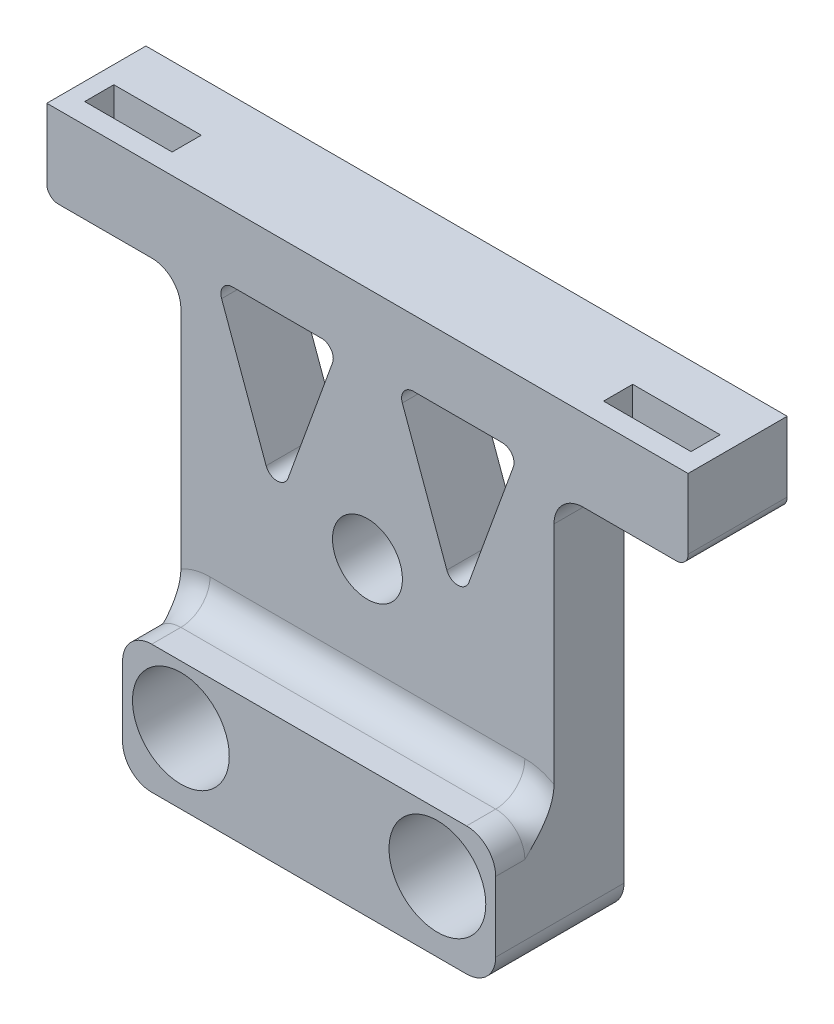
SolidWorks part; units mm, degrees
ref_plane "Front Plane" through (0, 0, 0) normal (0, 0, 1) x (1, 0, 0)
ref_plane "Top Plane" through (0, 0, 0) normal (0, 1, 0) x (1, 0, 0)
ref_plane "Right Plane" through (0, 0, 0) normal (1, 0, 0) x (0, 0, -1)
sketch "Esboço1" plane through (0, 0, 0) normal (0, 0, 1) x (1, 0, 0)
  line L0 (-194.983, 169.5286) -> (-202.6205, 148.5298)
  line L1 (-193, 100.2122) -> (-247, 100.2122)
  line L2 (-188, 105.2122) -> (-188, 164.5682)
  line L4 (-252, 105.2122) -> (-252, 164.5682)
  line L5 (-212.1375, 172.2122) -> (-196.8625, 172.2122)
  line L6 (-220, 183.5682) -> (-220, 100.2122) construction
  line L7 (-275, 183.5682) -> (-165, 183.5682)
  line L8 (-275, 183.5682) -> (-275, 171.5682)
  line L9 (-273, 169.5682) -> (-257, 169.5682)
  line L10 (-165, 183.5682) -> (-165, 171.5682)
  line L11 (-183, 169.5682) -> (-167, 169.5682)
  line L12 (-206.3795, 148.5298) -> (-214.017, 169.5286)
  line L13 (0, 100.2122) -> (-440, 100.2122) construction
  line L15 (-233.6205, 148.5298) -> (-225.983, 169.5286)
  line L16 (-227.8625, 172.2122) -> (-243.1375, 172.2122)
  line L17 (-245.017, 169.5286) -> (-237.3795, 148.5298)
  line L19 (-219, 172.2122) -> (-252, 172.2122) construction
  line L20 (-219, 172.2122) -> (-188, 172.2122) construction
  arc A0 (-202.6205, 148.5298) -> (-206.3795, 148.5298) centre (-204.5, 149.2135) cw
  arc A1 (-194.983, 169.5286) -> (-196.8625, 172.2122) centre (-196.8625, 170.2122) ccw
  arc A2 (-212.1375, 172.2122) -> (-214.017, 169.5286) centre (-212.1375, 170.2122) ccw
  circle A3 centre (-242, 112.2122) radius 8.3
  arc A4 (-225.983, 169.5286) -> (-227.8625, 172.2122) centre (-227.8625, 170.2122) ccw
  arc A5 (-243.1375, 172.2122) -> (-245.017, 169.5286) centre (-243.1375, 170.2122) ccw
  circle A6 centre (-198, 112.2122) radius 8.3
  arc A7 (-233.6205, 148.5298) -> (-237.3795, 148.5298) centre (-235.5, 149.2135) cw
  arc A8 (-167, 169.5682) -> (-165, 171.5682) centre (-167, 171.5682) ccw
  circle A9 centre (-220, 143.3622) radius 6
  arc A10 (-193, 100.2122) -> (-188, 105.2122) centre (-193, 105.2122) ccw
  arc A11 (-247, 100.2122) -> (-252, 105.2122) centre (-247, 105.2122) cw
  arc A12 (-188, 164.5682) -> (-183, 169.5682) centre (-183, 164.5682) cw
  arc A13 (-257, 169.5682) -> (-252, 164.5682) centre (-257, 164.5682) cw
  arc A14 (-275, 171.5682) -> (-273, 169.5682) centre (-273, 171.5682) ccw
  point P17 (-188, 100.2122)
  point P40 (-165, 169.5682)
  point P41 (-204.5, 143.3622)
  point P44 (-194.0069, 172.2122)
  point P47 (-214.9931, 172.2122)
  point P50 (-225.0069, 172.2122)
  point P53 (-245.9931, 172.2122)
  point P56 (-235.5, 143.3622)
  point P59 (-275, 169.5682)
  dimension "D6" = 5
  dimension "D9" = 5
  dimension "D10" = 2
  dimension "D11" = 2
  dimension "D4" = 10
  dimension "D5" = 10
  dimension "D7" = 110
  dimension "D8" = 14
  dimension "D1" = 43.15
  dimension "D2" = 12
  dimension "D3" = 12
extrude "Ressalto-extrusão1" add sketch "Esboço1" along normal blind 12
sketch "Esboço2" plane through (0, 0, 12) normal (0, 0, 1) x (1, 0, 0)
  line L6 (-252, 164.5682) -> (-252, 105.2122) construction
  line L7 (-247, 122.2122) -> (-193, 122.2122)
  line L8 (-252, 117.2122) -> (-252, 105.2122)
  line L9 (-247, 100.2122) -> (-193, 100.2122)
  line L10 (-188, 117.2122) -> (-188, 105.2122)
  line L11 (0, 100.2122) -> (-440, 100.2122) construction
  arc A0 (-193, 100.2122) -> (-188, 105.2122) centre (-193, 105.2122) ccw
  arc A1 (-193, 122.2122) -> (-188, 117.2122) centre (-193, 117.2122) cw
  arc A2 (-252, 105.2122) -> (-247, 100.2122) centre (-247, 105.2122) ccw
  arc A3 (-247, 122.2122) -> (-252, 117.2122) centre (-247, 117.2122) ccw
  circle A6 centre (-242, 112.2122) radius 8.3
  circle A7 centre (-242, 112.2122) radius 8.3
  circle A9 centre (-198, 112.2122) radius 8.3
  circle A10 centre (-198, 112.2122) radius 8.3
  point P10 (-188, 100.2122)
  point P13 (-188, 122.2122)
  point P18 (-252, 122.2122)
  dimension "D2" = 5
  dimension "D1" = 22
  dimension "D3" = 0
  dimension "D4" = 0
extrude "Ressalto-extrusão2" add sketch "Esboço2" along normal blind 10
fillet "Filete1" radius 5 3 edges at (-189.4645, 120.7477, 12) (-250.5355, 120.7477, 12) (-220, 122.2122, 12)
sketch "Esboço3" plane through (0, 169.5682, 0) normal (0, -1, 0) x (1, 0, 0)
  line L0 (-265, 12) -> (-265, 0) construction
  line L5 (-175, 12) -> (-175, 0) construction
  line L6 (-183, 12) -> (-167, 12) construction
  line L7 (-273, 12) -> (-257, 12) construction
  line L8 (-183, 12) -> (-183, 0) construction
  line L9 (-183, 0) -> (-167, 0) construction
  line L19 (-273, 0) -> (-257, 0) construction
  line L20 (-257, 12) -> (-257, 0) construction
  line L21 (-272, 8.5) -> (-257, 8.5)
  line L22 (-272, 8.5) -> (-272, 3.5)
  line L23 (-272, 3.5) -> (-257, 3.5)
  line L24 (-257, 8.5) -> (-257, 3.5)
  line L25 (-272, 6) -> (-257, 6) construction
  line L26 (-183, 8.5) -> (-168, 8.5)
  line L27 (-183, 8.5) -> (-183, 3.5)
  line L28 (-183, 3.5) -> (-168, 3.5)
  line L29 (-168, 8.5) -> (-168, 3.5)
  line L30 (-183, 6) -> (-168, 6) construction
  point P22 (-175, 6)
  point P31 (-265, 6)
  dimension "D1" = 5
  dimension "D2" = 15
  dimension "D3" = 5
extrude "Corte-extrusão1" cut sketch "Esboço3" against normal blind 15
sketch "Esboço5" plane through (0, 0, 0) normal (0, 0, -1) x (-1, 0, 0)
  line L8 (183.8551, 169.8918) -> (199.7305, 175.8987)
  line L9 (240.2695, 175.8987) -> (256.1449, 169.8918)
  line L10 (218.2305, 170.2377) -> (203.2695, 175.8987)
  line L11 (221.7695, 170.2377) -> (236.7305, 175.8987)
  line L16 (167, 169.5682) -> (183, 169.5682)
  line L17 (188, 164.5682) -> (188, 105.2122)
  line L18 (193, 100.2122) -> (247, 100.2122)
  line L19 (252, 105.2122) -> (252, 164.5682)
  line L20 (257, 169.5682) -> (273, 169.5682)
  line L21 (275, 171.5682) -> (275, 183.5682)
  line L22 (275, 183.5682) -> (165, 183.5682)
  line L23 (165, 183.5682) -> (165, 171.5682)
  line L24 (167, 169.5682) -> (182.0857, 169.5682)
  line L28 (257.9143, 169.5682) -> (273, 169.5682)
  line L29 (275, 171.5682) -> (275, 183.5682)
  line L30 (275, 183.5682) -> (165, 183.5682)
  line L31 (165, 183.5682) -> (165, 171.5682)
  arc A6 (256.1449, 169.8918) -> (257.9143, 169.5682) centre (257.9143, 174.5682) ccw
  arc A7 (236.7305, 175.8987) -> (240.2695, 175.8987) centre (238.5, 171.2222) cw
  arc A8 (218.2305, 170.2377) -> (221.7695, 170.2377) centre (220, 174.9141) ccw
  arc A9 (203.2695, 175.8987) -> (199.7305, 175.8987) centre (201.5, 171.2222) ccw
  arc A10 (182.0857, 169.5682) -> (183.8551, 169.8918) centre (182.0857, 174.5682) ccw
  arc A12 (165, 171.5682) -> (167, 169.5682) centre (167, 171.5682) ccw
  arc A13 (188, 164.5682) -> (183, 169.5682) centre (183, 164.5682) ccw
  arc A14 (188, 105.2122) -> (193, 100.2122) centre (193, 105.2122) ccw
  arc A15 (247, 100.2122) -> (252, 105.2122) centre (247, 105.2122) ccw
  arc A16 (257, 169.5682) -> (252, 164.5682) centre (257, 164.5682) ccw
  arc A17 (273, 169.5682) -> (275, 171.5682) centre (273, 171.5682) ccw
  arc A18 (165, 171.5682) -> (167, 169.5682) centre (167, 171.5682) ccw
  arc A23 (273, 169.5682) -> (275, 171.5682) centre (273, 171.5682) ccw
  dimension "D2" = 5
  dimension "D1" = 0
extrude "Ressalto-extrusão3" add sketch "Esboço5" along normal blind 5
